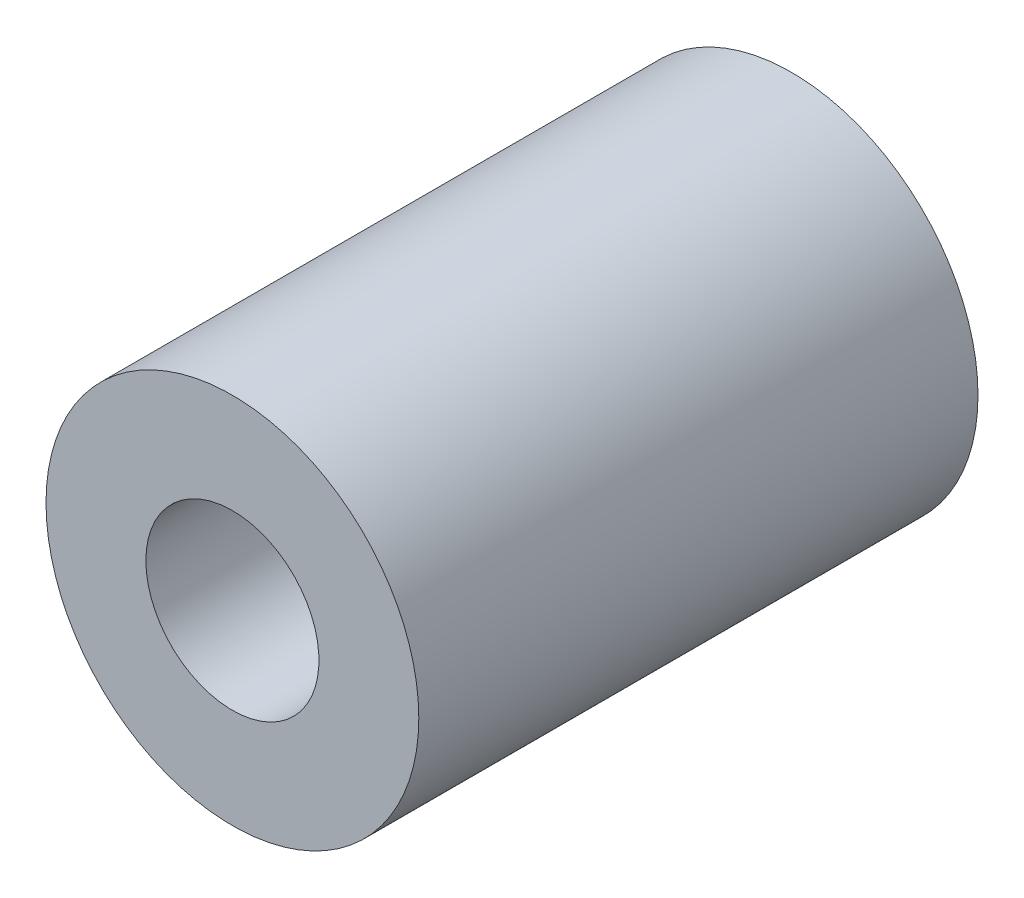
SolidWorks part; units mm, degrees
ref_plane "Plan de face" through (0, 0, 0) normal (0, 0, 1) x (1, 0, 0)
ref_plane "Plan de dessus" through (0, 0, 0) normal (0, 1, 0) x (1, 0, 0)
ref_plane "Plan de droite" through (0, 0, 0) normal (1, 0, 0) x (0, 0, -1)
sketch "Esquisse1" plane through (0, 0, 0) normal (0, 0, 1) x (1, 0, 0)
  line L1 (-0.9885, -3.25) -> (1.037, -3.25) construction
  circle A0 centre (0, 0) radius 7
  circle A1 centre (0, 0) radius 3.25
  point P3 (1.6604, 2.7576)
  dimension "D1" = 14
  dimension "D2" = 6.5
extrude "Boss.-Extru.1" add sketch "Esquisse1" along normal blind 21
